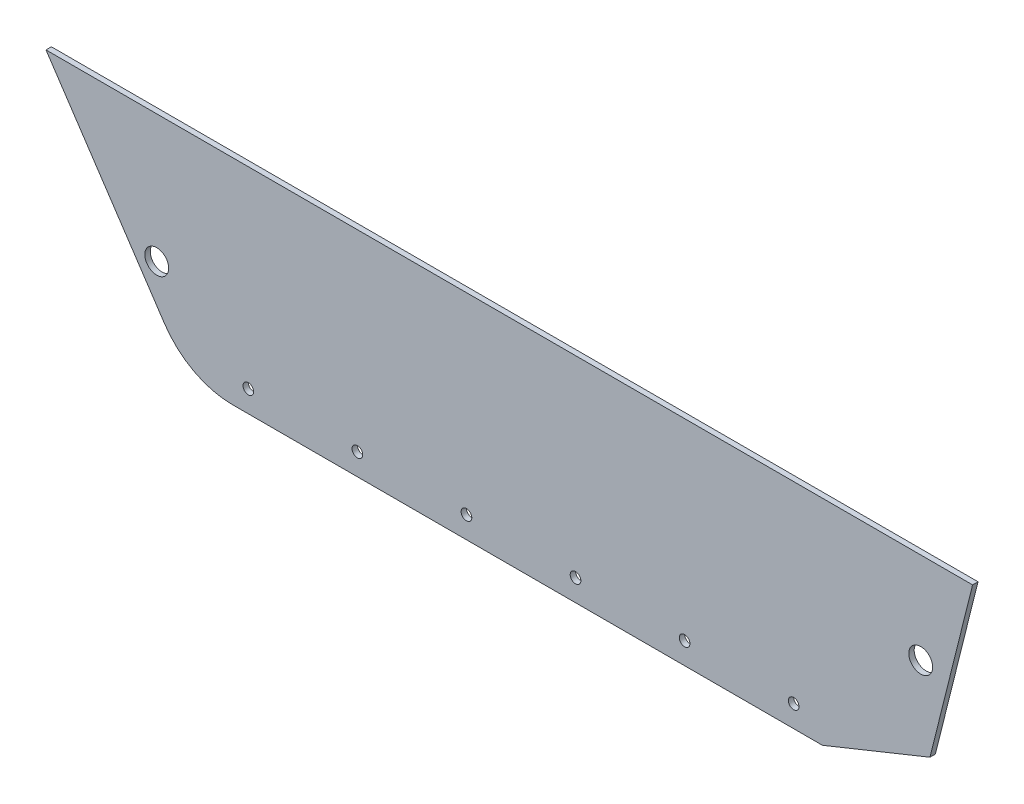
SolidWorks part; units mm, degrees
material "5052-H34"
ref_plane "Front Plane" through (0, 0, 0) normal (0, 0, 1) x (1, 0, 0)
ref_plane "Top Plane" through (0, 0, 0) normal (0, 1, 0) x (1, 0, 0)
ref_plane "Right Plane" through (0, 0, 0) normal (1, 0, 0) x (0, 0, -1)
sketch "Sketch1" plane through (0, 0, 0) normal (0, 0, 1) x (1, 0, 0)
  line L6 (-98.8794, 3.851) -> (-31.8794, -96.649)
  line L7 (428.1206, 28.9396) -> (403.1206, -71.149)
  line L9 (403.1206, -71.149) -> (366, -96.649)
  line L10 (-31.8794, -96.649) -> (366, -96.649)
  line L12 (-98.8794, 3.851) -> (-115.6052, 28.9396)
  line L13 (-115.6052, 28.9396) -> (428.1206, 28.9396)
  circle A0 centre (3.1206, -83.899) radius 3.125
  circle A1 centre (67.1206, -83.899) radius 3.125
  circle A2 centre (131.1206, -83.899) radius 3.125
  circle A3 centre (195.1206, -83.899) radius 3.125
  circle A4 centre (259.1206, -83.899) radius 3.125
  circle A5 centre (323.1206, -83.899) radius 3.125
  point P0 (-48.8794, -71.149)
  point P2 (-31.8794, -96.649)
  point P8 (48, -83.899)
  point P9 (403.1206, -71.149)
  dimension "D2" = 64
  dimension "D4" = 64
  dimension "D14" = 6.25
  dimension "D1" = 25.5
  dimension "D3" = 75
  dimension "D5" = 25
  dimension "D6" = 80
  dimension "D7" = 527
  dimension "D8" = 180
  dimension "D9" = 64
  dimension "D10" = 64
  dimension "D11" = 64
  dimension "D12" = 123.69
  dimension "D13" = 12.75
  dimension "D15" = 366
  dimension "D16" = 115.6052
extrude "Boss-Extrude1" add sketch "Sketch1" along normal blind 3.175 contours L12 L13 L7 L9 L10 L6
extrude "Cut-Extrude1" cut sketch "Sketch1<4>" along normal through all contours A0 | A1 | A2 | A3 | A4 | A5 region at (3.1206, -83.899, 0)
sketch "Sketch1<4>" plane through (0, 0, 0) normal (0, 0, 1) x (1, 0, 0) same geometry as "Sketch1"
sketch "Sketch5" plane through (0, 0, 0) normal (0, 0, -1) x (-1, 0, 0)
  line L0 (48.8794, -71.149) -> (-14.2353, -96.649)
  line L1 (31.8794, -96.649) -> (-366, -96.649) construction
  line L2 (-14.2353, -96.649) -> (31.8794, -96.649)
  line L3 (31.8794, -96.649) -> (48.8794, -71.149)
  line L6 (-366, -96.649) -> (-403.1206, -71.149)
  line L7 (-403.1206, -71.149) -> (-352, -71.149)
  line L9 (-352, -71.149) -> (-326.5, -96.649)
  line L11 (-366, -96.649) -> (-326.5, -96.649)
  dimension "D1" = 22
  dimension "D2" = 45
extrude "Cut-Extrude2" [suppressed] cut sketch "Sketch5" against normal up to next
sketch "Sketch6" plane through (0, 0, 3.175) normal (0, 0, 1) x (1, 0, 0)
  line L0 (-48.8794, -71.149) -> (14.2353, -96.649)
  line L1 (-31.8794, -96.649) -> (366, -96.649) construction
  line L2 (14.2353, -96.649) -> (-31.8794, -96.649)
  line L3 (-31.8794, -96.649) -> (-48.8794, -71.149)
  dimension "D1" = 158
fillet "Fillet1" radius 48 1 edges at (-31.8794, -96.649, 1.5875)
sketch "Sketch7" plane through (0, 0, 3.175) normal (0, 0, 1) x (1, 0, 0)
  line L0 (403.1206, -71.149) -> (340.0059, -96.649)
  line L1 (-31.8794, -96.649) -> (366, -96.649) construction
  line L2 (340.0059, -96.649) -> (366, -96.649)
  line L3 (366, -96.649) -> (403.1206, -71.149)
  dimension "D1" = 22
extrude "Cut-Extrude3" cut sketch "Sketch7" against normal blind 10
sketch "Sketch9" plane through (0, 0, 0) normal (0, 0, -1) x (-1, 0, 0)
  line L0 (-403.1206, -71.149) -> (48.8794, -71.149)
  line L1 (48.8794, -71.149) -> (48.8794, -114.9143)
  line L2 (48.8794, -114.9143) -> (-403.1206, -114.9143)
  line L3 (-403.1206, -114.9143) -> (-403.1206, -71.149)
sketch "Sketch11" plane through (0, 0, 0) normal (0, 0, -1) x (-1, 0, 0)
  circle A0 centre (-397.6786, -24.6104) radius 7
  dimension "D1" = 14
extrude "Cut-Extrude5" cut sketch "Sketch11" against normal up to next
sketch "Sketch13" plane through (0, 0, 0) normal (0, 0, -1) x (-1, 0, 0)
  line L0 (115.6052, 28.9396) -> (-428.1206, 28.9396) construction
  circle A0 centre (50.6052, -46.0604) radius 7
  dimension "D1" = 14
  dimension "D2" = 65
  dimension "D3" = 75
extrude "Cut-Extrude6" cut sketch "Sketch13" against normal blind 10
